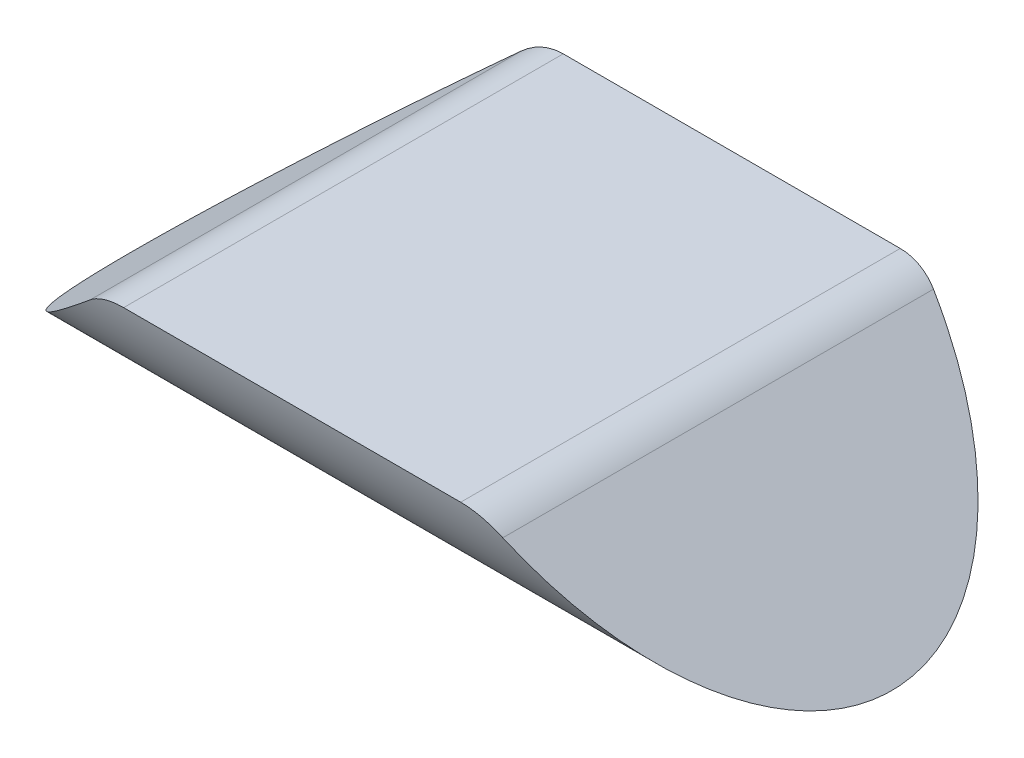
SolidWorks part; units mm, degrees
ref_plane "Front Plane" through (0, 0, 0) normal (0, 0, 1) x (1, 0, 0)
ref_plane "Top Plane" through (0, 0, 0) normal (0, 1, 0) x (1, 0, 0)
ref_plane "Right Plane" through (0, 0, 0) normal (1, 0, 0) x (0, 0, -1)
sketch "Sketch1" plane through (0, 0, 0) normal (1, 0, 0) x (0, 0, -1)
  line L2 (-73.4407, -20.32) -> (73.4407, -20.32)
  arc A0 (-73.4407, -20.32) -> (73.4407, -20.32) centre (0, 0) ccw
  dimension "D1" = 76.2
  dimension "D2" = 20.32
extrude "Boss-Extrude1" add sketch "Sketch1" along normal mid plane 254
sketch "Sketch7" plane through (0, 0, 0) normal (0, 0, 1) x (1, 0, 0)
  line L1 (-63.5, -20.32) -> (-127, -20.32)
  line L5 (-127, -76.2) -> (-63.5, -20.32)
  line L6 (127, -20.32) -> (-127, -20.32) construction
  line L7 (-127, -20.32) -> (-127, -76.2) construction
  line L8 (-127, -20.32) -> (-127, -76.2)
  point P4 (0, -20.32)
  dimension "D1" = 63.5
extrude "Cut-Extrude3" cut sketch "Sketch7" against normal through all both and the other way through all
mirror "Mirror4" about plane through (0, 0, 0) normal (1, 0, 0) of "Cut-Extrude3"
fillet "Fillet3" radius 19.05 2 edges at (63.5, -20.32, 0) (-63.5, -20.32, 0)
split "Split1" trim tools "Right Plane" bodies to split 109 resulting bodies 111 112
combine bodies "Combine1" operation type add bodies to combine 112 111
